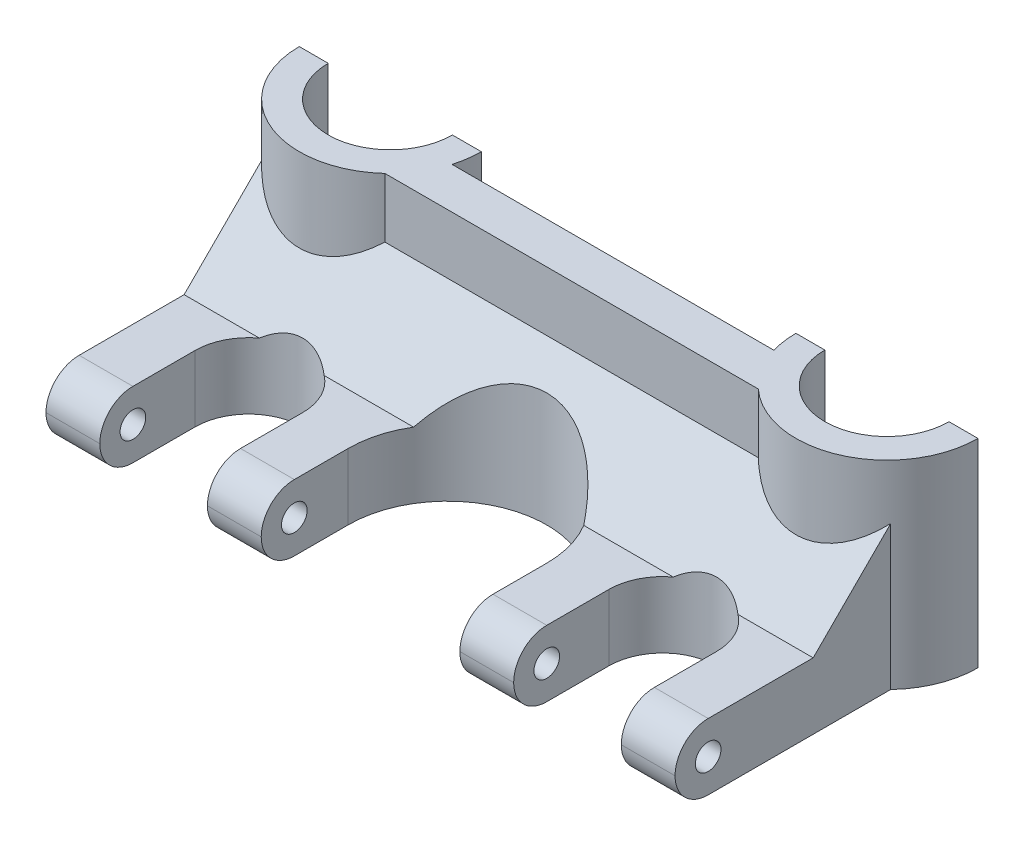
SolidWorks part; units mm, degrees
material "ABS"
ref_plane "Front Plane" through (0, 0, 0) normal (0, 0, 1) x (1, 0, 0)
ref_plane "Top Plane" through (0, 0, 0) normal (0, 1, 0) x (1, 0, 0)
ref_plane "Right Plane" through (0, 0, 0) normal (1, 0, 0) x (0, 0, -1)
sketch "Sketch1" plane through (0, 0, 0) normal (0, 1, 0) x (1, 0, 0)
  line L1 (-25, -2.5) -> (25, -2.5)
  line L2 (-25, -2.5) -> (-25, 2.5)
  line L3 (-25, 2.5) -> (25, 2.5)
  line L4 (25, -2.5) -> (25, 2.5)
  line L5 (-25, -2.5) -> (25, 2.5) construction
  line L6 (-25, 2.5) -> (25, -2.5) construction
  point P0 (0, 0)
  dimension "D1" = 50
  dimension "D2" = 5
extrude "Boss-Extrude1" add sketch "Sketch1" along normal blind 24
sketch "Sketch5" plane through (0, 0, 0) normal (0, 1, 0) x (1, 0, 0)
  line L1 (-38, -8) -> (38, -8)
  line L2 (-38, -8) -> (-38, -28)
  line L3 (-38, -28) -> (38, -28)
  line L4 (38, -8) -> (38, -28)
  line L5 (-38, -8) -> (38, -28) construction
  line L6 (-38, -28) -> (38, -8) construction
  point P0 (0, -18)
  dimension "D1" = 76
  dimension "D2" = 20
  dimension "D3" = 18
extrude "Boss-Extrude3" add sketch "Sketch5" along normal blind 8 separate body
sketch "Sketch6" plane through (0, 0, 0) normal (1, 0, 0) x (0, 0, -1)
  line L0 (-11.3137, 8) -> (0, -3.3137) construction
  line L1 (-11.3137, 8) -> (0, 19.3137)
  line L2 (0, -3.3137) -> (11.3137, 8) construction
  line L3 (0, 19.3137) -> (11.3137, 8) construction
  line L4 (-11.3137, 8) -> (11.3137, 8) construction
  line L5 (0, -3.3137) -> (0, 19.3137) construction
  line L6 (-8, 8) -> (-28, 8) construction
  line L7 (-8, 8) -> (-8, 0) construction
  line L8 (-11.3137, 8) -> (-11.3137, 0)
  line L9 (-28, 0) -> (-8, 0) construction
  line L10 (-11.3137, 0) -> (2.5, 0)
  line L11 (2.5, 0) -> (2.5, 19.3137)
  line L12 (2.5, 24) -> (2.5, 0) construction
  line L13 (2.5, 19.3137) -> (0, 19.3137)
  point P0 (-18, 8)
  point P1 (0, 8)
  point P8 (-8, 4)
  dimension "D1" = 16
  dimension "D2" = 18
  dimension "D3" = 4
extrude "Boss-Extrude4" add sketch "Sketch6" along normal up to surface and the other way up to surface up to face at (38, 4, 18) other way up to face at (-38, 4, 18)
sketch "Sketch7" plane through (0, 8, 0) normal (0, 1, 0) x (1, 0, 0)
  line L0 (-38, -28) -> (38, -28) construction
  line L1 (-12, -17.5) -> (-12, -28)
  line L2 (-31.5, -16.5) -> (-31.5, -28)
  line L3 (-31.5, -28) -> (-18.5, -28)
  line L4 (-18.5, -16.5) -> (-18.5, -28)
  line L5 (-12, -28) -> (12, -28)
  line L6 (12, -28) -> (12, -17.5)
  arc A0 (-18.5, -16.5) -> (-31.5, -16.5) centre (-25, -16.5) ccw
  arc A1 (12, -17.5) -> (-12, -17.5) centre (0, -17.5) ccw
  dimension "D2" = 13
  dimension "D4" = 24
  dimension "D1" = 25
  dimension "D3" = 16.5
  dimension "D5" = 17.5
extrude "Cut-Extrude4" cut sketch "Sketch7" against normal through all and the other way through all
mirror "Mirror2" about plane through (0, 0, 0) normal (1, 0, 0) of "Cut-Extrude4"
fillet "Fillet1" radius 4 8 edges at (34.75, 0, 28) (-34.75, 0, 28) (-34.75, 8, 28) (34.75, 8, 28) (15.25, 0, 28) (15.25, 8, 28) (-15.25, 0, 28) (-15.25, 8, 28)
sketch "Sketch8" plane through (38, 0, 0) normal (1, 0, 0) x (0, 0, -1)
  circle A0 centre (-24, 4) radius 1.55
  dimension "D1" = 3.1
extrude "Cut-Extrude5" cut sketch "Sketch8" against normal through all
sketch "Sketch2" plane through (0, 0, 0) normal (0, 1, 0) x (1, 0, 0)
  line L0 (19, 5.6) -> (41, 5.6)
  arc A0 (19, 5.6) -> (41, 5.6) centre (30, 5.6) ccw
  dimension "D2" = 11
  dimension "D1" = 5.6
  dimension "D3" = 30
extrude "Boss-Extrude2" add sketch "Sketch2" along normal up to surface (24 mm away) up to face at (0, 24, 0)
sketch "Sketch4" plane through (0, 0, 0) normal (0, 1, 0) x (1, 0, 0)
  line L0 (19, 5.6) -> (41, 5.6) construction
  circle A0 centre (30, 5.6) radius 7.5
  dimension "D1" = 15
extrude "Cut-Extrude3" cut sketch "Sketch4" along normal through all
mirror "Mirror1" about plane through (0, 0, 0) normal (1, 0, 0) of "Cut-Extrude3", "Boss-Extrude2"
